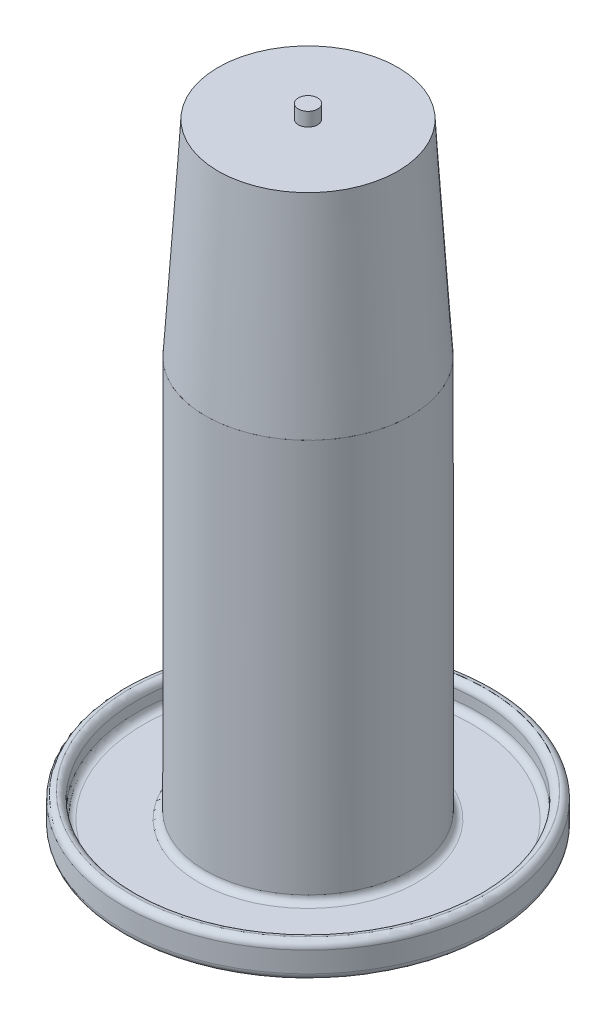
SolidWorks part; units mm, degrees
ref_plane "Front Plane" through (0, 0, 0) normal (0, 0, 1) x (1, 0, 0)
ref_plane "Top Plane" through (0, 0, 0) normal (0, 1, 0) x (1, 0, 0)
ref_plane "Right Plane" through (0, 0, 0) normal (1, 0, 0) x (0, 0, -1)
sketch "Sketch2" plane through (0, 0, 0) normal (0, 0, 1) x (1, 0, 0)
  line L3 (-68.58, 0) -> (0, 0)
  line L4 (-68.58, 12.7) -> (-68.58, 0)
  line L5 (0, 0) -> (0, 152.4)
  line L6 (-68.58, 12.7) -> (-63.4394, 12.7)
  line L7 (-63.4394, 12.7) -> (-63.4394, 3.81)
  line L8 (-63.4394, 3.81) -> (-38.1, 3.81)
  line L9 (-38.1, 3.81) -> (-38.1, 152.4)
  line L10 (-38.1, 152.4) -> (0, 152.4)
  line L11 (-38.1, 152.4) -> (0, 152.4)
  dimension "D7" = 8.89
  dimension "D1" = 38.1
  dimension "D2" = 152.4
  dimension "D3" = 12.7
  dimension "D4" = 30.48
  dimension "D5" = 68.58
  dimension "D6" = 5.1406
revolve "Revolve1" add sketch "Sketch2" angle 360 about L5 region at (-20.0768, 74.2341, 0)
shell "Shell1" thickness 2.54 removed face at (0, 152.4, -38.1)
sketch "Sketch4" plane through (0, 0, 0) normal (0, 0, 1) x (1, 0, 0)
  line L2 (0, 228.6) -> (0, 152.4)
  line L3 (38.1, 152.4) -> (-38.1, 152.4) construction
  line L5 (0, 228.6) -> (-33.346, 228.6)
  line L6 (-33.346, 228.6) -> (-38.1, 152.4)
  line L7 (-38.1, 152.4) -> (0, 152.4)
  dimension "D1" = 76.2
  dimension "D2" = 3.57
revolve "Revolve2" add sketch "Sketch4" angle 360 about L2
sketch "Sketch5" plane through (0, 228.6, 0) normal (0, 1, 0) x (1, 0, 0)
  circle A0 centre (0, 0) radius 3.5814
  dimension "D1" = 7.1628
extrude "Boss-Extrude1" add sketch "Sketch5" along normal blind 5.08
shell "Shell12" thickness 2.54 removed face at (-38.1, 152.4, 0)
fillet "Fillet1" radius 2.54 2 edges at (0, 0, -68.58) (0, 12.7, -68.58)
fillet "Fillet3" radius 2.54 3 edges at (0, 3.81, -38.1) (0, 3.81, -63.4394) (0, 12.7, -63.4394)
